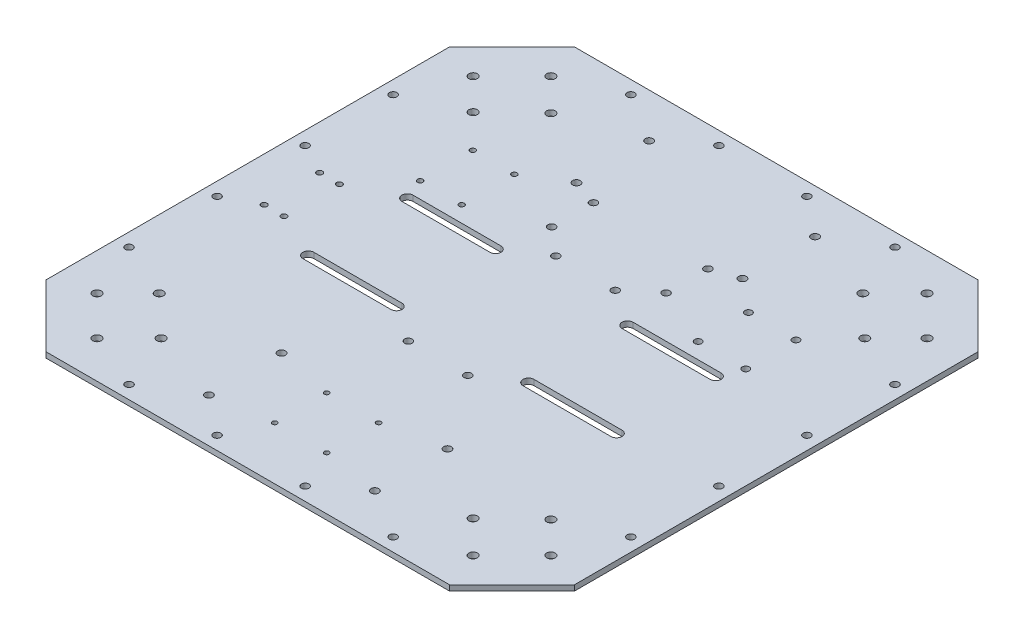
SolidWorks part; units mm, degrees
ref_plane "Front Plane" through (0, 0, 0) normal (0, 0, 1) x (1, 0, 0)
ref_plane "Top Plane" through (0, 0, 0) normal (0, 1, 0) x (1, 0, 0)
ref_plane "Right Plane" through (0, 0, 0) normal (1, 0, 0) x (0, 0, -1)
sketch "Sketch1" plane through (0, 0, 0) normal (0, 1, 0) x (1, 0, 0)
  line L0 (-61.766, 15.7353) -> (-25.845, 51.6564)
  line L1 (-61.766, 51.6564) -> (243.034, 51.6564)
  line L2 (-61.766, 51.6564) -> (-61.766, -253.1436)
  line L3 (-61.766, -253.1436) -> (243.034, -253.1436)
  line L4 (243.034, 51.6564) -> (243.034, -253.1436)
  line L5 (90.634, 95.069) -> (90.634, -294.9418) construction
  line L6 (-86.5248, -100.7436) -> (277.558, -100.7436) construction
  line L7 (243.034, 15.7353) -> (207.1129, 51.6564)
  line L8 (243.034, -217.2226) -> (207.1129, -253.1436)
  line L9 (-61.766, -217.2226) -> (-25.845, -253.1436)
  line L10 (128.734, -72.1686) -> (179.534, -72.1686) construction
  line L11 (128.734, -68.9936) -> (179.534, -68.9936)
  line L12 (128.734, -75.3436) -> (179.534, -75.3436)
  line L13 (128.734, -129.3186) -> (179.534, -129.3186) construction
  line L14 (128.734, -132.4936) -> (179.534, -132.4936)
  line L15 (128.734, -126.1436) -> (179.534, -126.1436)
  line L16 (52.534, -129.3186) -> (1.734, -129.3186) construction
  line L17 (52.534, -132.4936) -> (1.734, -132.4936)
  line L18 (52.534, -126.1436) -> (1.734, -126.1436)
  line L19 (52.534, -72.1686) -> (1.734, -72.1686) construction
  line L20 (52.534, -68.9936) -> (1.734, -68.9936)
  line L21 (52.534, -75.3436) -> (1.734, -75.3436)
  arc A0 (128.734, -68.9936) -> (128.734, -75.3436) centre (128.734, -72.1686) ccw
  arc A1 (179.534, -75.3436) -> (179.534, -68.9936) centre (179.534, -72.1686) ccw
  arc A2 (128.734, -132.4936) -> (128.734, -126.1436) centre (128.734, -129.3186) cw
  arc A3 (179.534, -126.1436) -> (179.534, -132.4936) centre (179.534, -129.3186) cw
  arc A4 (52.534, -132.4936) -> (52.534, -126.1436) centre (52.534, -129.3186) ccw
  arc A5 (1.734, -126.1436) -> (1.734, -132.4936) centre (1.734, -129.3186) ccw
  arc A6 (52.534, -68.9936) -> (52.534, -75.3436) centre (52.534, -72.1686) cw
  arc A7 (1.734, -75.3436) -> (1.734, -68.9936) centre (1.734, -72.1686) cw
  point P8 (90.634, 51.6564)
  point P11 (-61.766, -100.7436)
  point P18 (154.134, -72.1686)
  point P27 (154.134, -129.3186)
  point P34 (27.134, -129.3186)
  point P41 (27.134, -72.1686)
  dimension "D6" = 6.35
  dimension "D1" = 304.8
  dimension "D2" = 304.8
  dimension "D3" = 45
  dimension "D4" = 50.8
  dimension "D5" = 50.8
  dimension "D7" = 38.1
  dimension "D8" = 50.8
extrude "Boss-Extrude1" add sketch "Sketch1" along normal blind 3.175 contours L2 L9 L3 L8 L4 L7 L1 L0 A5 L18 A4 L17 A1 L12 A0 L11 L15 A3 L14 A2 L21 A7 L20 A6 region at (90.634, 0, 100.7436)
sketch "Sketch2" plane through (0, 3.175, 0) normal (0, 1, 0) x (1, 0, 0)
  line L0 (-40.323, 7.7627) -> (-22.3625, -10.1978) construction
  line L1 (-17.8724, 30.2133) -> (0.6409, 11.7001) construction
  line L2 (-43.8055, 33.6958) -> (20.8232, -30.9329) construction
  line L3 (-61.766, 15.7353) -> (-25.845, 51.6564) construction
  line L7 (90.634, 51.6564) -> (90.634, -253.1436) construction
  line L8 (-25.845, 51.6564) -> (207.1129, 51.6564) construction
  line L9 (-25.845, -253.1436) -> (207.1129, -253.1436) construction
  line L10 (-61.766, -100.7436) -> (243.034, -100.7436) construction
  line L11 (-61.766, 15.7353) -> (-61.766, -217.2226) construction
  line L12 (243.034, 15.7353) -> (243.034, -217.2226) construction
  circle A0 centre (-17.8724, 30.2133) radius 2.4638
  circle A1 centre (0.6409, 11.7001) radius 2.4638
  circle A2 centre (-22.3625, -10.1978) radius 2.4638
  circle A3 centre (-40.323, 7.7627) radius 2.4638
  circle A4 centre (203.6304, -10.1978) radius 2.4638
  circle A5 centre (221.5909, 7.7627) radius 2.4638
  circle A6 centre (180.627, 11.7001) radius 2.4638
  circle A7 centre (199.1403, 30.2133) radius 2.4638
  circle A8 centre (-22.3625, -191.2895) radius 2.4638
  circle A9 centre (-40.323, -209.25) radius 2.4638
  circle A10 centre (-17.8724, -231.7006) radius 2.4638
  circle A11 centre (0.6409, -213.1873) radius 2.4638
  circle A12 centre (221.5909, -209.25) radius 2.4638
  circle A13 centre (199.1403, -231.7006) radius 2.4638
  circle A14 centre (180.627, -213.1873) radius 2.4638
  circle A15 centre (203.6304, -191.2895) radius 2.4638
  dimension "D3" = 4.9276
  dimension "D4" = 4.9276
  dimension "D5" = 4.9276
  dimension "D6" = 4.9276
  dimension "D1" = 25.4
  dimension "D2" = 31.75
  dimension "D7" = 15.875
extrude "Cut-Extrude1" cut sketch "Sketch2" against normal blind 6.35
sketch "Sketch3" plane through (0, 3.175, 0) normal (0, 1, 0) x (1, 0, 0)
  line L0 (-61.766, -100.7436) -> (278.5513, -100.7436) construction
  line L2 (-61.766, 15.7353) -> (-61.766, -217.2226) construction
  line L3 (90.634, 51.6564) -> (90.634, -273.1997) construction
  line L4 (-25.845, 51.6564) -> (207.1129, 51.6564) construction
  circle A0 centre (73.362, -58.1986) radius 2.159
  circle A1 centre (107.652, -58.1986) radius 2.159
  circle A2 centre (73.362, -143.2886) radius 2.159
  circle A3 centre (107.652, -143.2886) radius 2.159
  point P10 (-61.766, -100.7436)
  dimension "D3" = 4.318
  dimension "D4" = 4.318
  dimension "D5" = 4.318
  dimension "D6" = 4.318
  dimension "D1" = 34.29
  dimension "D2" = 85.09
  dimension "D7" = 42.545
  dimension "D8" = 17.272
extrude "Cut-Extrude2" cut sketch "Sketch3" against normal blind 6.35
sketch "Sketch4" plane through (0, 3.175, 0) normal (0, 1, 0) x (1, 0, 0)
  line L0 (90.634, 51.6564) -> (90.634, -36.4614) construction
  line L1 (-25.845, 51.6564) -> (207.1129, 51.6564) construction
  line L2 (-61.766, -100.7436) -> (257.447, -100.7436) construction
  line L3 (-61.766, 15.7353) -> (-61.766, -217.2226) construction
  circle A0 centre (42.755, 26.2564) radius 2.2225
  circle A1 centre (138.513, 26.2564) radius 2.2225
  circle A2 centre (42.755, -15.6536) radius 2.2225
  circle A3 centre (138.513, -15.6536) radius 2.2225
  circle A4 centre (138.513, -185.8336) radius 2.2225
  circle A5 centre (42.755, -185.8336) radius 2.2225
  circle A6 centre (138.513, -227.7436) radius 2.2225
  circle A7 centre (42.755, -227.7436) radius 2.2225
  dimension "D1" = 4.445
  dimension "D2" = 4.445
  dimension "D3" = 4.445
  dimension "D4" = 4.445
  dimension "D5" = 95.758
  dimension "D6" = 41.91
  dimension "D7" = 47.879
  dimension "D8" = 25.4
extrude "Cut-Extrude3" cut sketch "Sketch4" against normal through all
sketch "Sketch5" plane through (0, 3.175, 0) normal (0, 1, 0) x (1, 0, 0)
  line L0 (-61.766, -100.7436) -> (105.2484, -100.7436) construction
  line L1 (-61.766, 15.7353) -> (-61.766, -217.2226) construction
  circle A0 centre (-36.366, -84.7416) radius 1.651
  circle A1 centre (-24.936, -84.7416) radius 1.651
  circle A2 centre (-24.936, -116.7456) radius 1.651
  circle A3 centre (-36.366, -116.7456) radius 1.651
  dimension "D1" = 3.302
  dimension "D2" = 3.302
  dimension "D3" = 11.43
  dimension "D4" = 16.002
  dimension "D5" = 25.4
extrude "Cut-Extrude4" cut sketch "Sketch5" against normal through all
sketch "Sketch6" plane through (0, 3.175, 0) normal (0, 1, 0) x (1, 0, 0)
  line L0 (243.034, 15.7353) -> (243.034, -217.2226) construction
  line L1 (-25.845, 51.6564) -> (207.1129, 51.6564) construction
  line L2 (90.634, 51.6564) -> (90.634, -253.1436) construction
  line L3 (-25.845, -253.1436) -> (207.1129, -253.1436) construction
  line L4 (-61.766, 15.7353) -> (-61.766, -217.2226) construction
  circle A0 centre (157.182, -30.8936) radius 2.032
  circle A1 centre (157.182, -59.8496) radius 2.032
  circle A2 centre (184.614, -59.8496) radius 2.032
  circle A3 centre (184.614, -30.8936) radius 2.032
  circle A4 centre (57.614, -20.7336) radius 2.159
  circle A5 centre (57.614, -44.8636) radius 2.159
  circle A6 centre (123.654, -44.8636) radius 2.159
  circle A7 centre (123.654, -20.7336) radius 2.159
  circle A8 centre (75.648, -192.6916) radius 1.397
  circle A9 centre (75.648, -222.6636) radius 1.397
  circle A10 centre (105.62, -222.6636) radius 1.397
  circle A11 centre (105.62, -192.6916) radius 1.397
  circle A12 centre (-3.389, -29.3696) radius 1.55
  circle A13 centre (-3.346, -59.7696) radius 1.55
  circle A14 centre (20.6111, -29.3696) radius 1.55
  circle A15 centre (20.6111, -59.7696) radius 1.55
  dimension "D1" = 4.064
  dimension "D6" = 4.318
  dimension "D7" = 4.318
  dimension "D10" = 2.794
  dimension "D11" = 2.794
  dimension "D15" = 3.1
  dimension "D16" = 3.1
  dimension "D18" = 3.1
  dimension "D19" = 3.1
  dimension "D2" = 27.432
  dimension "D3" = 28.956
  dimension "D4" = 58.42
  dimension "D5" = 82.55
  dimension "D8" = 33.02
  dimension "D9" = 24.13
  dimension "D12" = 14.986
  dimension "D13" = 29.972
  dimension "D14" = 30.48
  dimension "D17" = 30.4
  dimension "D20" = 24
  dimension "D21" = 72.39
  dimension "D22" = 58.42
  dimension "D23" = 81.026
extrude "Cut-Extrude5" cut sketch "Sketch6" against normal through all
sketch "Sketch7" plane through (0, 3.175, 0) normal (0, 1, 0) x (1, 0, 0)
  line L0 (90.634, 51.6564) -> (90.634, -272.7763) construction
  line L1 (-25.845, 51.6564) -> (207.1129, 51.6564) construction
  line L2 (-61.766, -100.7436) -> (338.9555, -100.7436) construction
  line L3 (-61.766, 15.7353) -> (-61.766, -217.2226) construction
  circle A0 centre (65.234, 44.0364) radius 2.159
  circle A1 centre (14.434, 44.0364) radius 2.159
  circle A2 centre (-54.146, -75.3436) radius 2.159
  circle A3 centre (-54.146, -24.5436) radius 2.159
  circle A4 centre (235.414, -24.5436) radius 2.159
  circle A5 centre (235.414, -75.3436) radius 2.159
  circle A6 centre (166.834, 44.0364) radius 2.159
  circle A7 centre (116.034, 44.0364) radius 2.159
  circle A8 centre (116.034, -245.5236) radius 2.159
  circle A9 centre (166.834, -245.5236) radius 2.159
  circle A10 centre (235.414, -126.1436) radius 2.159
  circle A11 centre (235.414, -176.9436) radius 2.159
  circle A12 centre (-54.146, -176.9436) radius 2.159
  circle A13 centre (-54.146, -126.1436) radius 2.159
  circle A14 centre (14.434, -245.5236) radius 2.159
  circle A15 centre (65.234, -245.5236) radius 2.159
  point P16 (0, 0)
  dimension "D1" = 4.318
  dimension "D2" = 4.318
  dimension "D6" = 4.318
  dimension "D7" = 4.318
  dimension "D3" = 25.4
  dimension "D4" = 50.8
  dimension "D5" = 7.62
  dimension "D8" = 25.4
  dimension "D9" = 50.8
  dimension "D10" = 7.62
extrude "Cut-Extrude6" cut sketch "Sketch7" against normal through all
